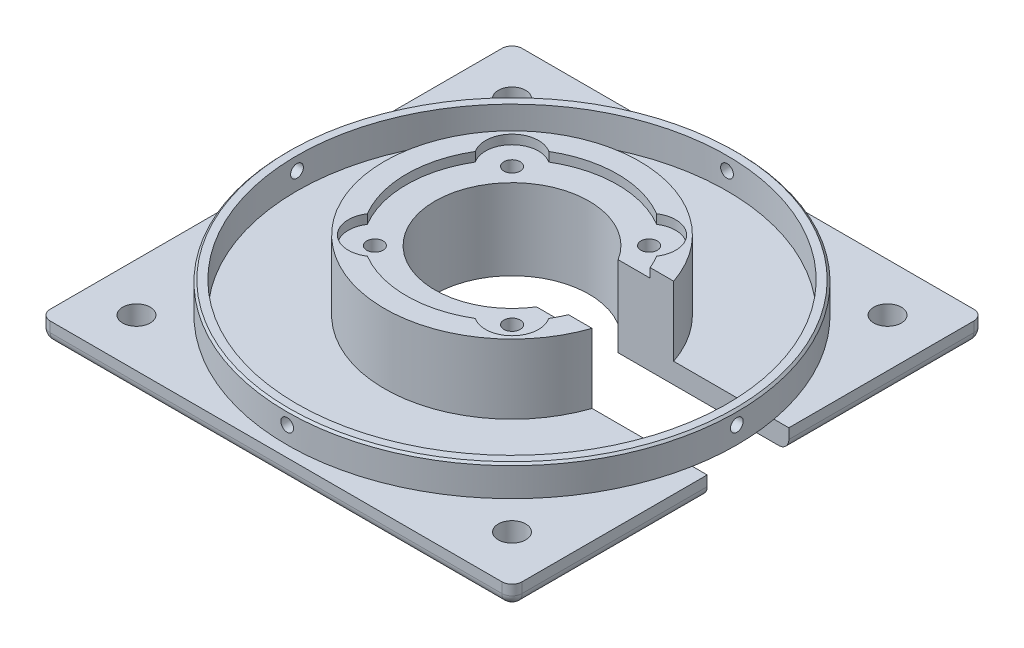
SolidWorks part; units mm, degrees
ref_plane "Front Plane" through (0, 0, 0) normal (0, 0, 1) x (1, 0, 0)
ref_plane "Top Plane" through (0, 0, 0) normal (0, 1, 0) x (1, 0, 0)
ref_plane "Right Plane" through (0, 0, 0) normal (1, 0, 0) x (0, 0, -1)
sketch "Sketch3" plane through (0, 0, 0) normal (0, 1, 0) x (1, 0, 0)
  circle A0 centre (0, 0) radius 7.55
  circle A1 centre (0, 0) radius 12.5
  dimension "D1" = 15.1
  dimension "D2" = 25
extrude "Boss-Extrude2" add sketch "Sketch3" along normal blind 8.8
sketch "Sketch4" plane through (0, 8.8, 0) normal (0, 1, 0) x (1, 0, 0)
  line L0 (6.4033, 4) -> (6.4033, -4)
  line L1 (6.4033, -4) -> (13.2817, -4)
  line L2 (13.2817, -4) -> (13.2817, 4)
  line L3 (13.2817, 4) -> (6.4033, 4)
  circle A0 centre (0, 0) radius 7.55 construction
  point P0 (0, 0)
  point P1 (6.4033, 4)
  point P3 (6.4033, -4)
  dimension "D1" = 4
extrude "Cut-Extrude2" cut sketch "Sketch4" against normal blind 8.8
sketch "Sketch5" plane through (0, 8.8, 0) normal (0, 1, 0) x (1, 0, 0)
  line L0 (0, 0) -> (17.4279, 0) construction
  line L1 (0, 0) -> (-11.2462, -11.2462) construction
  line L2 (0, 0) -> (-11.0539, 11.0539) construction
  point P0 (0, 0)
  point P1 (-6.715, 6.72)
  point P3 (-6.715, -6.72)
  point P9 (6.72, -6.715)
  point P10 (6.72, 6.715)
  dimension "D1" = 6.72
  dimension "D2" = 9.5
  dimension "D3" = 6.72
  dimension "D4" = 9.5
sketch "Sketch6" plane through (0, 8.8, 0) normal (0, 1, 0) x (1, 0, 0)
  line L0 (0, 0) -> (-11.2462, -11.2462) construction
  line L1 (0, 0) -> (-11.0539, 11.0539) construction
  line L2 (0, 0) -> (17.4279, 0) construction
  point P0 (5.2883, -8.8853)
  point P9 (-8.8853, 5.2883)
  point P12 (5.2883, 8.8853)
  point P14 (8.8893, -5.2817)
  point P15 (-5.2817, 8.8893)
  point P16 (8.8893, 5.2817)
  point P17 (-5.2817, -8.8893)
  point P18 (-8.8853, -5.2883)
  dimension "D1" = 2.6
  dimension "D2" = 10.34
  dimension "D3" = 2.6
  dimension "D4" = 10.34
sketch "Sketch8" plane through (0, 8.8, 0) normal (0, 1, 0) x (1, 0, 0)
  circle A0 centre (0, 0) radius 10.34
extrude "Cut-Extrude5" cut sketch "Sketch8" against normal blind 0.9
hole_wizard "Tap Drill for M2x0.4 Tap1" positions "3DSketch1" profile "Sketch10" hole size "M2x0.4" standard "ANSI Metric" end condition through all
sketch3d "3DSketch1"
  point P0 (6.72, 8.8, 6.715)
  point P3 (-6.715, 8.8, 6.72)
  point P6 (-6.715, 8.8, -6.72)
  point P9 (6.72, 8.8, -6.715)
sketch "Sketch10" plane through (6.72, 8.8, 6.715) normal (1, 0, 0) x (0, 0, 1)
  line L0 (0, 0) -> (0, 8.8)
  line L1 (0, 8.8) -> (0.8, 8.8)
  line L2 (0.8, 8.8) -> (0.8, 0)
  line L5 (0.8, 0) -> (0, 0)
  line L11 (0, -6.35) -> (0, 107.95) construction
  dimension "Thru Hole Dia." = 1.6
  dimension "Thru Hole Depth" = 8.8
sketch "Sketch11" plane through (0, 8.8, 0) normal (0, 1, 0) x (1, 0, 0)
  line L0 (8.8893, 5.2817) -> (5.2883, 8.8853)
  line L1 (8.8893, -5.2817) -> (5.2883, -8.8853)
  line L2 (-5.2817, -8.8893) -> (-8.8853, -5.2883)
  line L3 (-5.2817, 8.8893) -> (-8.8853, 5.2883)
  arc A0 (5.2883, -8.8853) -> (8.8893, -5.2817) centre (6.72, -6.715) ccw
  arc A1 (9.535, 4) -> (9.535, -4) centre (0, 0) ccw construction
  arc A2 (8.8893, 5.2817) -> (5.2883, 8.8853) centre (6.72, 6.715) ccw
  arc A3 (-5.2817, 8.8893) -> (-8.8853, 5.2883) centre (-6.715, 6.72) ccw
  arc A4 (-8.8853, -5.2883) -> (-5.2817, -8.8893) centre (-6.715, -6.72) ccw
extrude "Cut-Extrude6" cut sketch "Sketch11" against normal blind 0.9
sketch "Sketch12" plane through (0, 0, 0) normal (0, -1, 0) x (1, 0, 0)
  line L0 (0, 0) -> (17.7684, 0) construction
  line L1 (0, 0) -> (0, 18.0241) construction
  line L2 (23.125, -23.125) -> (-23.125, -23.125)
  line L3 (-23.125, -23.125) -> (-23.125, 23.125)
  line L4 (-23.125, 23.125) -> (23.125, 23.125)
  line L9 (6.4033, 4) -> (23.125, 4)
  line L11 (23.125, -4) -> (6.4033, -4)
  line L13 (23.125, -23.125) -> (23.125, -4)
  line L14 (23.125, 23.125) -> (23.125, 4)
  arc A0 (6.4033, -4) -> (6.4033, 4) centre (0, 0) cw
  arc A1 (6.4033, 4) -> (6.4033, -4) centre (0, 0) ccw construction
  point P0 (23.125, -23.125)
  point P4 (23.125, 23.125)
  point P5 (-23.125, 23.125)
  point P7 (-23.125, -23.125)
  dimension "D1" = 23.125
  dimension "D2" = 23.125
extrude "Boss-Extrude4" add sketch "Sketch12" against normal blind 2
fillet "Fillet2" radius 1 2 edges at (-23.125, 0, 0) (0, 0, 23.125)
fillet "Fillet3" radius 1 2 edges at (-22.8321, 0.2929, 22.8321) (-23.125, 1.5, 23.125)
sketch "Sketch13" plane through (0, 0, 0) normal (0, -1, 0) x (1, 0, 0)
  line L0 (0, 0) -> (-25.0462, 0) construction
  line L1 (0, 0) -> (0, 26.5218) construction
  point P0 (18.3989, -18.3989)
  point P5 (18.3989, 18.3989)
  point P6 (-18.3989, -18.3989)
  point P7 (-18.3989, 18.3989)
  dimension "D1" = 18.3989
  dimension "D2" = 18.3989
hole_wizard "M2.5 Clearance Hole1" positions "3DSketch2" profile "Sketch14" hole size "M2.5" standard "ANSI Metric" end condition through all
sketch3d "3DSketch2"
  point P0 (18.3989, 0, 18.3989)
  point P3 (18.3989, 0, -18.3989)
  point P6 (-18.3989, 0, -18.3989)
  point P9 (-18.3989, 0, 18.3989)
  point P12 (0, 0, 0)
sketch "Sketch14" plane through (18.3989, 0, 18.3989) normal (1, 0, 0) x (0, 0, -1)
  line L0 (0, 0) -> (0, 8.8)
  line L1 (0, 8.8) -> (1.35, 8.8)
  line L2 (1.35, 8.8) -> (1.35, 0)
  line L5 (1.35, 0) -> (0, 0)
  line L11 (0, -6.35) -> (0, 107.95) construction
  dimension "Thru Hole Dia." = 2.7
  dimension "Thru Hole Depth" = 8.8
fillet "Fillet4" radius 1 7 edges at (23.125, 1.5, 23.125) (23.125, 0.2929, 22.8321) (-23.125, 1.5, -23.125) (-22.8321, 0.2929, -23.125) (23.125, 0, 13.0625) (23.125, 0, -13.5625) (0.5, 0, -23.125)
fillet "Fillet5" radius 1 2 edges at (22.8321, 0.2929, -22.8321) (23.125, 1.5, -23.125)
sketch "Sketch15" plane through (0, 2, 0) normal (0, 1, 0) x (1, 0, 0)
  circle A0 centre (0, 0) radius 22.0375
  circle A1 centre (0, 0) radius 21.075
  point P0 (0, 0)
extrude "Boss-Extrude6" add sketch "Sketch15" along normal blind 3
hole_wizard "Tap Drill for M1.6x0.35 Tap1" positions "3DSketch4" profile "Sketch25" hole size "M1.6x0.35" standard "ANSI Metric" end condition up to next
sketch3d "3DSketch4"
  point P0 (22.0375, 3.7, 0)
sketch "Sketch25" plane through (22.0375, 3.7, 0) normal (0, 1, 0) x (0, 0, -1)
  line L0 (0, 0) -> (0, 0.9625)
  line L1 (0, 0.9625) -> (0.625, 0.9625)
  line L2 (0.625, 0.9625) -> (0.625, 0)
  line L5 (0.625, 0) -> (0, 0)
  line L11 (0, -6.35) -> (0, 107.95) construction
  dimension "Thru Hole Dia." = 1.25
  dimension "Thru Hole Depth" = 0.9625
ref_axis "Axis1" through (0, 7.9, 0) along (0, -1, 0)
pattern_circular "CirPattern1" count 4 over 360 about axis through (0, 7.9, 0) along (0, -1, 0) of "Tap Drill for M1.6x0.35 Tap1"
chamfer "Chamfer1" distance 0.2 angle 45 1 edges at (0, 5, 22.0375)
